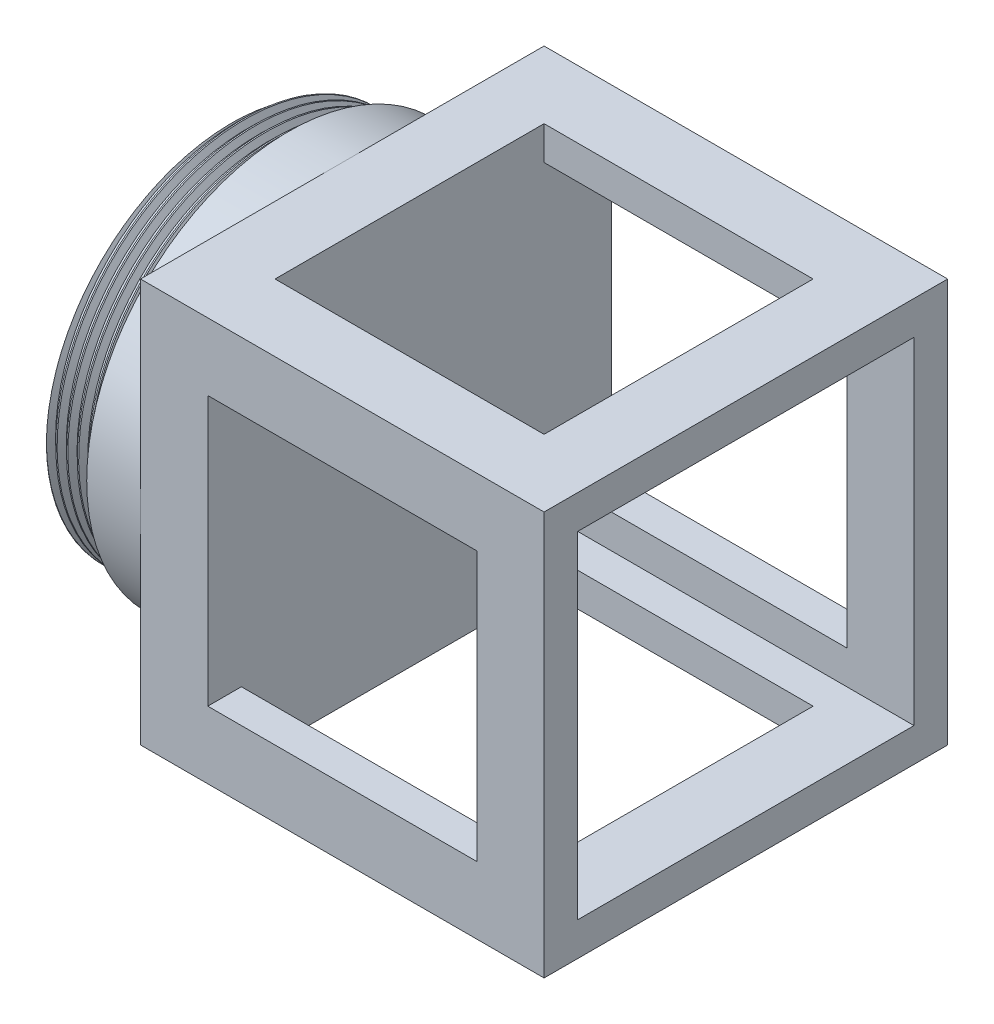
SolidWorks part; units mm, degrees
ref_plane "Front Plane" through (0, 0, 0) normal (0, 0, 1) x (1, 0, 0)
ref_plane "Top Plane" through (0, 0, 0) normal (0, 1, 0) x (1, 0, 0)
ref_plane "Right Plane" through (0, 0, 0) normal (1, 0, 0) x (0, 0, -1)
sketch "Sketch1" plane through (0, 0, 0) normal (0, 0, 1) x (1, 0, 0)
  line L1 (-37.5, -37.5) -> (37.5, -37.5)
  line L2 (-37.5, -37.5) -> (-37.5, 37.5)
  line L3 (-37.5, 37.5) -> (37.5, 37.5)
  line L4 (37.5, -37.5) -> (37.5, 37.5)
  line L5 (-37.5, -37.5) -> (37.5, 37.5) construction
  line L6 (-37.5, 37.5) -> (37.5, -37.5) construction
  line L7 (-25, -25) -> (25, -25)
  line L8 (-25, -25) -> (-25, 25)
  line L9 (-25, 25) -> (25, 25)
  line L10 (25, -25) -> (25, 25)
  line L11 (-25, -25) -> (25, 25) construction
  line L12 (-25, 25) -> (25, -25) construction
  point P0 (0, 0)
  point P6 (0, 0)
  dimension "D1" = 75
  dimension "D2" = 50
extrude "Boss-Extrude1" add sketch "Sketch1" along normal mid plane 75
sketch "Sketch2" plane through (0, 37.5, 0) normal (0, 1, 0) x (1, 0, 0)
  line L1 (-25, -25) -> (25, -25)
  line L2 (-25, -25) -> (-25, 25)
  line L3 (-25, 25) -> (25, 25)
  line L4 (25, -25) -> (25, 25)
  line L5 (-25, -25) -> (25, 25) construction
  line L6 (-25, 25) -> (25, -25) construction
  point P0 (0, 0)
  dimension "D1" = 50
extrude "Cut-Extrude1" cut sketch "Sketch2" against normal up to surface (75 mm away) up to face at (0, -37.5, 0)
sketch "Sketch3" plane through (37.5, 0, 0) normal (1, 0, 0) x (0, 0, -1)
  line L1 (-31.25, -31.25) -> (31.25, -31.25)
  line L2 (-31.25, -31.25) -> (-31.25, 31.25)
  line L3 (-31.25, 31.25) -> (31.25, 31.25)
  line L4 (31.25, -31.25) -> (31.25, 31.25)
  line L5 (-31.25, -31.25) -> (31.25, 31.25) construction
  line L6 (-31.25, 31.25) -> (31.25, -31.25) construction
  point P0 (0, 0)
  dimension "D1" = 62.5
extrude "Cut-Extrude2" cut sketch "Sketch3" against normal up to surface (62.5 mm away) up to face at (-25, 0, 0)
sketch "Sketch4" plane through (-37.5, 0, 0) normal (-1, 0, 0) x (0, 0, 1)
  circle A0 centre (0, 0) radius 37.5
  dimension "D1" = 75
extrude "Boss-Extrude2" add sketch "Sketch4" along normal blind 10
sketch "Sketch5" plane through (-47.5, 0, 0) normal (-1, 0, 0) x (0, 0, 1)
  circle A0 centre (0, 0) radius 32.5
  circle A1 centre (0, 0) radius 35
  dimension "D1" = 70
  dimension "D2" = 65
extrude "Boss-Extrude3" add sketch "Sketch5" along normal blind 10
thread "Thread4" pitch 2 method cut profile "Thread Profile2" start angle 0, offset 1, length 0, pitch 2, diameter 70
ref_plane "Plane2" through (-58.5, 0, -35) normal (0, -1, 0) x (0, 0, -1)
sketch "Thread Profile2" plane through (-58.5, 0, -35) normal (0, -1, 0) x (0, 0, -1)
  line L0 (0, 0) -> (0, 2) construction
  line L11 (0, 0) -> (0, 1.75)
  line L12 (0, 1.75) -> (-1.0825, 1.125)
  line L13 (-1.0825, 1.125) -> (-1.0825, 0.625)
  line L15 (-1.0825, 0.625) -> (0, 0)
  line L17 (-1.0825, 0.875) -> (0, 0.875) construction
  point P2 (0, 0)
  dimension "Pitch" = 2
  dimension "Profile_Angle" = 60
  dimension "Profile_Land" = 0.5
  dimension "Profile_Height" = 1.0825
